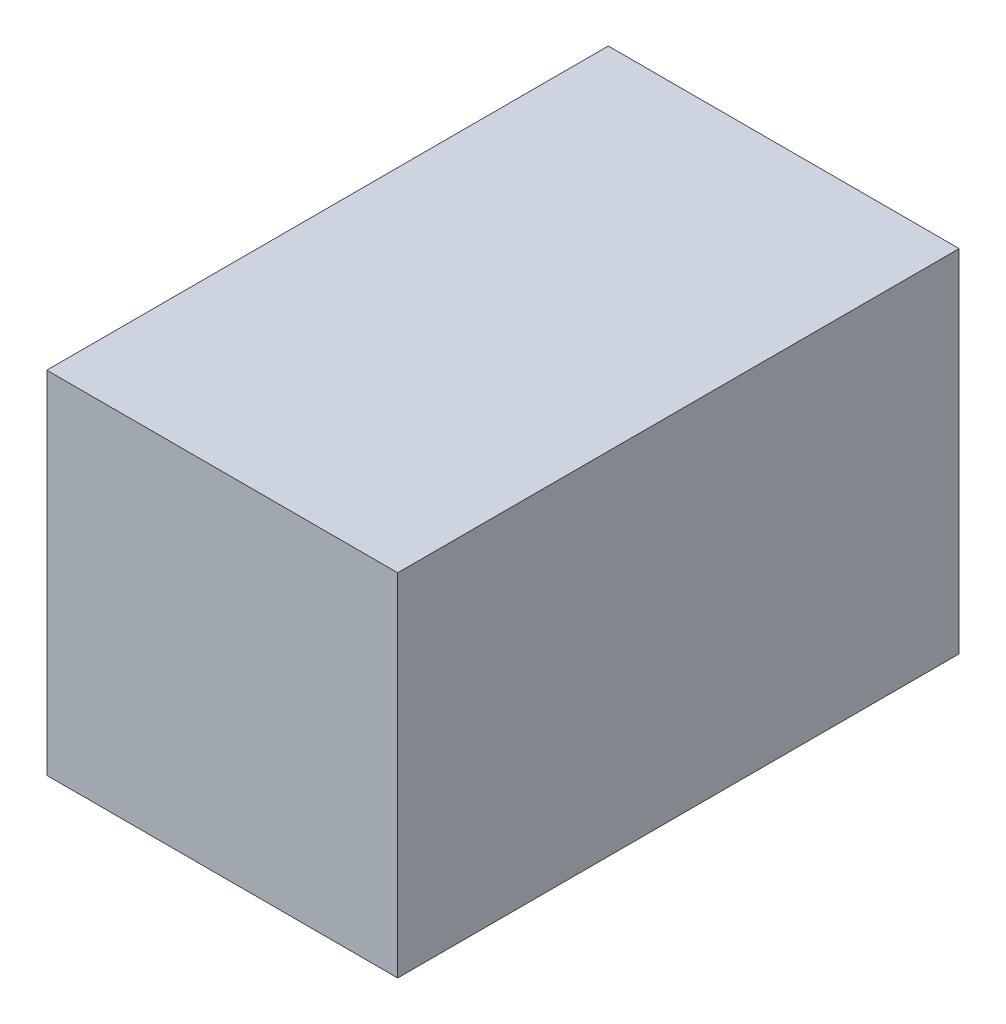
SolidWorks part; units mm, degrees
ref_plane "Front" through (0, 0, 0) normal (0, 0, 1) x (1, 0, 0)
ref_plane "Top" through (0, 0, 0) normal (0, 1, 0) x (1, 0, 0)
ref_plane "Right" through (0, 0, 0) normal (1, 0, 0) x (0, 0, -1)
sketch "sketch1" plane through (0, 0, 0) normal (0, 0, 1) x (1, 0, 0)
  line L0 (1.1906, 1.1906) -> (-1.1906, -1.1906) construction
  line L1 (-1.1906, 1.1906) -> (1.1906, 1.1906)
  line L2 (-1.1906, 1.1906) -> (-1.1906, -1.1906)
  line L3 (-1.1906, -1.1906) -> (1.1906, -1.1906)
  line L4 (1.1906, 1.1906) -> (1.1906, -1.1906)
  dimension "W" = 2.3813
  dimension "H" = 2.3813
extrude "Extrude1" add sketch "sketch1" along normal blind 3.81
